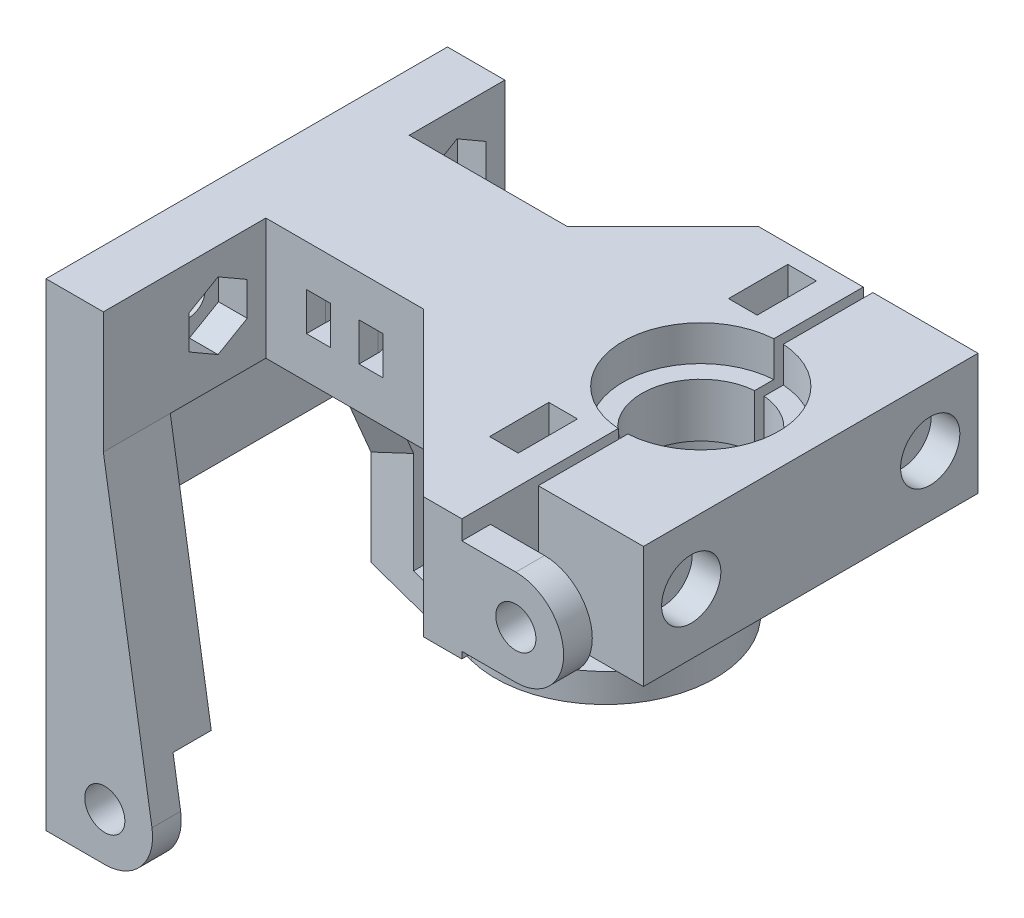
SolidWorks part; units mm, degrees
note: The reader was unsure of these and kept them because the rebuilt part matched: shared geometry of "草圖14<3>", "草圖43<3>", "草圖34<5>", "草圖48<3>".
ref_plane "前基準面" through (0, 0, 0) normal (0, 0, 1) x (1, 0, 0)
ref_plane "上基準面" through (0, 0, 0) normal (0, 1, 0) x (1, 0, 0)
ref_plane "右基準面" through (0, 0, 0) normal (1, 0, 0) x (0, 0, -1)
sketch "草圖13" plane through (0, 0, 0) normal (0, 1, 0) x (1, 0, 0)
  line L0 (0, 0) -> (44, 0) construction
  line L1 (0, 0) -> (0, 17.5)
  line L2 (0, 0) -> (0, -17.5)
  line L3 (0, 17.5) -> (6, 17.5)
  line L4 (6, 17.5) -> (6, -17.5)
  line L5 (6, -17.5) -> (0, -17.5)
  line L6 (6, 7.5) -> (32.5, 7.5)
  line L7 (6, -7.5) -> (32.5, -7.5)
  line L8 (32.5, 17.5) -> (22.5, 7.5)
  line L9 (32.5, -17.5) -> (55.5, -17.5)
  line L10 (32.5, -17.5) -> (32.5, 17.5)
  line L11 (32.5, 17.5) -> (55.5, 17.5)
  line L12 (55.5, -17.5) -> (55.5, 17.5)
  line L13 (32.5, -17.5) -> (55.5, 17.5) construction
  line L14 (32.5, 17.5) -> (55.5, -17.5) construction
  line L15 (32.5, -17.5) -> (22.5, -7.5)
  line L16 (32.5, 7.5) -> (22.5, 7.5)
  line L17 (22.5, -7.5) -> (32.5, -7.5)
  circle A0 centre (44, 0) radius 8.15
  circle A1 centre (44, 0) radius 6.15
  point P17 (44, 0)
  dimension "D4" = 35
  dimension "D5" = 12.3
  dimension "D6" = 23
  dimension "D1" = 16.3
  dimension "D2" = 35
  dimension "D3" = 6
  dimension "D7" = 15
  dimension "D8" = 10
  dimension "D9" = 44
extrude "填料-伸長4" add sketch "草圖13" against normal blind 12.7
sketch "草圖17" plane through (0, 0, 0) normal (0, 1, 0) x (1, 0, 0)
  circle A0 centre (44, 0) radius 6.15
  circle A1 centre (44, 0) radius 8.15
  circle A2 centre (44, 0) radius 6.15 construction
  circle A3 centre (44, 0) radius 8.15 construction
  circle M29 centre (44, 0) radius 6.15
ref_plane "平面4" through (44, 0, 0) normal (-1, 0, 0) x (0, 0, 1)
sketch "草圖14" plane through (55.5, 0, 0) normal (-1, 0, 0) x (0, 0, 1)
  line L0 (17.5, -6.35) -> (7.5, -6.35) construction
  line L3 (-7.5, -6.35) -> (-17.5, -6.35) construction
  line L5 (-17.5, -12.7) -> (-17.5, 0) construction
  line L6 (17.5, -12.7) -> (17.5, 0) construction
  line L9 (7.5, -12.7) -> (7.5, 0) construction
  line L10 (-7.5, -12.7) -> (-7.5, 0) construction
  circle A0 centre (-12.5, -6.35) radius 1.65
  circle A1 centre (12.5, -6.35) radius 1.65
  circle A2 centre (12.5, -6.35) radius 3.1
  circle A3 centre (-12.5, -6.35) radius 3.1
  dimension "D1" = 3.3
  dimension "D2" = 6.2
sketch "草圖15" plane through (44, 0, 0) normal (-1, 0, 0) x (0, 0, 1)
  line L1 (17.5, 0) -> (-17.5, 0)
  line L2 (17.5, 0) -> (17.5, -12.7)
  line L3 (17.5, -12.7) -> (-17.5, -12.7)
  line L4 (-17.5, 0) -> (-17.5, -12.7)
extrude "除料-伸長11" cut sketch "草圖15" against normal blind 0.5 and the other way blind 0.5
extrude "除料-伸長12" cut sketch "草圖14" along normal blind 3 contours A3 A0 | A2 A1
extrude "除料-伸長13" cut sketch "草圖14<3>" along normal blind 25 contours A0 | A1
sketch "草圖14<3>" plane through (55.5, 0, 0) normal (-1, 0, 0) x (0, 0, 1) same geometry as "草圖14"
ref_plane "平面5" through (37.5, 0, 0) normal (1, 0, 0) x (0, 0, -1)
sketch "草圖16" plane through (37.5, 0, 0) normal (1, 0, 0) x (0, 0, -1)
  line L0 (-17.5, 0) -> (17.5, 0) construction
  line L1 (-15.6, -12.7) -> (-9.4, -12.7)
  line L2 (-15.6, -12.7) -> (-15.6, 0)
  line L3 (-15.6, 0) -> (-9.4, 0)
  line L4 (-9.4, -12.7) -> (-9.4, 0)
  line L5 (-15.6, -12.7) -> (-9.4, 0) construction
  line L6 (-15.6, 0) -> (-9.4, -12.7) construction
  line L8 (9.4, -12.7) -> (15.6, -12.7)
  line L9 (9.4, -12.7) -> (9.4, 0)
  line L10 (9.4, 0) -> (15.6, 0)
  line L11 (15.6, -12.7) -> (15.6, 0)
  line L12 (9.4, -12.7) -> (15.6, 0) construction
  line L13 (9.4, 0) -> (15.6, -12.7) construction
  point P0 (-12.5, -6.35)
  point P8 (12.5, -6.35)
  dimension "D1" = 6.2
extrude "除料-伸長14" cut sketch "草圖16" along normal blind 3
extrude "除料-伸長30" cut sketch "草圖17" against normal blind 3.7 contours A1 M29
sketch "草圖18" plane through (0, -12.7, 0) normal (0, -1, 0) x (1, 0, 0)
  circle A0 centre (44, 0) radius 8.15
  circle A1 centre (44, 0) radius 8.15 construction
  circle A2 centre (44, 0) radius 6.15
  circle A3 centre (44, 0) radius 6.15 construction
  line M5 (43.5, 6.1296) -> (43.5, 17.5)
  line M17 (43.5, -17.5) -> (43.5, -6.1296)
  arc M18 (43.5, -6.1296) -> (43.5, 6.1296) centre (44, 0) cw
extrude "除料-伸長31" cut sketch "草圖18" against normal blind 3.4 contours A2 A0 M17 M5 | A0 M5 M17 M18
sketch "草圖19" plane through (0, 0, 0) normal (-1, 0, 0) x (0, 0, 1)
  line L0 (0, 0) -> (0, -12.7) construction
  line L1 (17.5, -12.7) -> (-17.5, -12.7) construction
  line L2 (-12.5, -6.35) -> (12.5, -6.35) construction
  circle A0 centre (-12.5, -6.35) radius 1.65
  circle A1 centre (12.5, -6.35) radius 1.65
  point P8 (0, -6.35)
  dimension "D2" = 3.3
  dimension "D1" = 25
extrude "除料-伸長32" cut sketch "草圖19" against normal up to surface (6 mm away) up to face at (6, -6.35, 12.5)
sketch "草圖20" plane through (6, 0, 0) normal (1, 0, 0) x (0, 0, -1)
  line L1 (-12.5, -2.8282) -> (-15.55, -4.5891)
  line L2 (-15.55, -4.5891) -> (-15.55, -8.1109)
  line L3 (-15.55, -8.1109) -> (-12.5, -9.8718)
  line L4 (-12.5, -9.8718) -> (-9.45, -8.1109)
  line L5 (-9.45, -8.1109) -> (-9.45, -4.5891)
  line L6 (-9.45, -4.5891) -> (-12.5, -2.8282)
  line L7 (12.5, -2.8282) -> (9.45, -4.5891)
  line L8 (9.45, -4.5891) -> (9.45, -8.1109)
  line L9 (9.45, -8.1109) -> (12.5, -9.8718)
  line L10 (12.5, -9.8718) -> (15.55, -8.1109)
  line L11 (15.55, -8.1109) -> (15.55, -4.5891)
  line L12 (15.55, -4.5891) -> (12.5, -2.8282)
  circle A0 centre (-12.5, -6.35) radius 3.05 construction
  circle A1 centre (12.5, -6.35) radius 3.05 construction
  dimension "D1" = 6.1
extrude "除料-伸長33" cut sketch "草圖20" against normal blind 3
sketch "草圖21" plane through (0, -12.7, 0) normal (0, -1, 0) x (1, 0, 0)
  line L0 (0, -17.5) -> (6, -17.5) construction
  line L1 (0, 17.5) -> (3, 17.5)
  line L2 (0, 17.5) -> (0, -17.5)
  line L3 (0, -17.5) -> (3, -17.5)
  line L4 (3, 17.5) -> (3, -17.5)
  dimension "D1" = 3
extrude "填料-伸長5" add sketch "草圖21" along normal blind 10
ref_plane "平面6" through (0, 0, 24.5) normal (0, 0, 1) x (1, 0, 0)
sketch "草圖22" plane through (0, 0, 24.5) normal (0, 0, 1) x (1, 0, 0)
  line L0 (0, 0) -> (0, -50)
  line L1 (0, -50) -> (6.15, -50)
  line L2 (6.15, -45) -> (49.15, -45) construction
  line L3 (49.15, -45) -> (49.15, -7) construction
  line L4 (0, 0) -> (6, 0)
  line L5 (6, -12.7) -> (11.0861, -44.2031)
  line L6 (6, 0) -> (6, -12.7)
  line L8 (49.15, -2) -> (43.5, -2)
  line L10 (43.5, -12.7) -> (43.5, 0) construction
  line L11 (43.5, -2) -> (43.5, 0)
  line L13 (43.5, 0) -> (38, 0)
  line L14 (32.5, 0) -> (43.5, 0) construction
  line L15 (38, 0) -> (38, -12.7)
  line L16 (32.5, -12.7) -> (43.5, -12.7) construction
  line L17 (38, -12.7) -> (43.5, -12.7)
  line L18 (43.5, -12.7) -> (43.5, -12)
  line L19 (43.5, -12) -> (49.15, -12)
  circle A0 centre (49.15, -7) radius 2.1
  circle A1 centre (6.15, -45) radius 2.1
  circle A2 centre (6.15, -45) radius 5
  circle A3 centre (49.15, -7) radius 5
  dimension "D5" = 4.2
  dimension "D4" = 10
  dimension "D1" = 38
  dimension "D2" = 43
  dimension "D3" = 45
  dimension "D6" = 6.15
ref_plane "平面9" through (0, -6.35, 0) normal (0, 1, 0) x (1, 0, 0)
extrude "填料-伸長6" add sketch "草圖22" against normal up to surface (7 mm away)
sketch "草圖41" plane through (0, 0, 17.5) normal (0, 0, -1) x (-1, 0, 0)
  line L1 (-13.6797, -50.7245) -> (1.3797, -50.7245)
  line L2 (-13.6797, -50.7245) -> (-13.6797, -39.2755)
  line L3 (-13.6797, -39.2755) -> (1.3797, -39.2755)
  line L4 (1.3797, -50.7245) -> (1.3797, -39.2755)
  line L5 (-13.6797, -50.7245) -> (1.3797, -39.2755) construction
  line L6 (-13.6797, -39.2755) -> (1.3797, -50.7245) construction
  point P0 (-6.15, -45)
extrude "除料-伸長34" cut sketch "草圖41" against normal blind 4
sketch "草圖42" plane through (0, -2, 0) normal (0, 1, 0) x (1, 0, 0)
  line L0 (54.15, -24.5) -> (54.15, -17.5) construction
  line L1 (43.5, -17.5) -> (54.15, -17.5)
  line L2 (43.5, -17.5) -> (43.5, -21.5)
  line L3 (43.5, -21.5) -> (54.15, -21.5)
  line L4 (54.15, -17.5) -> (54.15, -21.5)
  dimension "D1" = 4
extrude "除料-伸長35" cut sketch "草圖42" against normal up to surface (10 mm away) up to face at (45.96, -12, 20.3)
sketch "草圖43" plane through (0, 0, 0) normal (0, 1, 0) x (1, 0, 0)
  line L0 (32.5, -17.5) -> (39.5, -24.5)
  line L1 (43.5, -24.5) -> (38, -24.5) construction
  line L2 (39.5, -24.5) -> (32.5, -24.5)
  line L3 (32.5, -17.5) -> (32.5, -24.5)
  line L4 (32.5, -17.5) -> (38, -17.5)
  line L5 (38, -17.5) -> (38, -23)
  line L6 (38, -17.5) -> (38, -24.5) construction
  line L7 (32.5, -17.5) -> (22.5, -7.5) construction
  line M16 (32.5, -17.5) -> (38, -17.5)
  line M17 (38, -17.5) -> (38, -24.5)
  line M18 (38, -24.5) -> (43.5, -24.5)
extrude "除料-伸長36" cut sketch "草圖43" against normal up to surface (12.7 mm away) contours L0 M17 M18 up to face at (23.8969, -12.7, 1.9688)
extrude "填料-伸長7" add sketch "草圖43<3>" against normal up to surface (12.7 mm away) contours L0 M16 M17 up to face at (39, -12.7, -12.5)
sketch "草圖43<3>" plane through (0, 0, 0) normal (0, 1, 0) x (1, 0, 0) same geometry as "草圖43"
sketch "草圖34" plane through (6, 0, 0) normal (1, 0, 0) x (0, 0, -1)
  line L0 (17.5, -12.7) -> (9.5, -12.7)
  line L1 (9.5, -22.7) -> (9.5, -42.7)
  line L2 (9.5, -42.7) -> (24.5, -42.7)
  line L3 (17.5, -16.2009) -> (24.5, -32.7)
  line L4 (17.5, -12.7) -> (8.1346, -12.7) construction
  line L5 (9.5, -12.7) -> (9.5, -22.7)
  line L6 (9.5, -32.7) -> (5.2574, -22.7)
  line L7 (17.5, -12.7) -> (24.5, -12.7)
  line L8 (24.5, -12.7) -> (24.5, -42.7)
  line L9 (17.5, -22.7) -> (-17.5, -22.7) construction
  line L10 (5.2574, -22.7) -> (9.5, -22.7)
  line L11 (17.5, -22.7) -> (17.5, -12.7) construction
  line L12 (-17.5, -12.7) -> (17.5, -12.7) construction
  line L13 (5.2574, -22.7) -> (5.2574, -12.7)
  line L14 (-8.1346, -12.7) -> (8.1346, -12.7) construction
  line L15 (5.2574, -12.7) -> (9.5, -12.7)
  line L16 (9.5, -12.7) -> (9.4752, -12.712)
  line L17 (17.5, -12.7) -> (17.5, -16.2009)
  line L18 (9.5, -22.7) -> (17.5, -22.7)
  line L19 (17.5, -22.7) -> (17.5, -16.2009)
  dimension "D1" = 20
  dimension "D2" = 3.5009
  dimension "D3" = 8
  dimension "D4" = 10
  dimension "D5" = 20
  dimension "D6" = 7
extrude "填料-伸長8" add sketch "草圖34" against normal up to surface (6 mm away) contours L19 L18 L1 L2 L8 L3 | L10 L6 L1 up to face at (0, -6.35, 14.15)
sketch "草圖44" plane through (0, -42.7, 0) normal (0, -1, 0) x (1, 0, 0)
  line L0 (0, -24.5) -> (14.134, -28.1372)
  line L1 (0, -9.5) -> (14.134, -5.8628)
  line L2 (0, -9.5) -> (0, -24.5)
  line L5 (0, -9.5) -> (6, -9.5) construction
  line L6 (0, -24.5) -> (0, -9.5) construction
  circle A0 centre (17, -17) radius 11.5
  circle A1 centre (17, -17) radius 6.5
  line M1 (0, -9.5) -> (0, -24.5)
  line M2 (0, -24.5) -> (6, -24.5)
  line M3 (6, -24.5) -> (6, -9.5)
  line M4 (6, -9.5) -> (0, -9.5)
  dimension "D2" = 13
  dimension "D3" = 23
  dimension "D1" = 17
  dimension "D4" = 17
extrude "填料-伸長9" add sketch "草圖44" against normal blind 3 contours A0 A1 M3 | A0 M3 | A0 M3 M4 M1 M2 | A0 L0 M3 M2 | A0 L1 M4 M3
extrude "填料-伸長14" add sketch "草圖34<5>" against normal up to surface (3 mm away) up to face at (3, -19.9501, -6.7096)
sketch "草圖34<5>" plane through (6, 0, 0) normal (1, 0, 0) x (0, 0, -1) same geometry as "草圖34"
sketch "草圖39" plane through (0, -6.35, 0) normal (0, 1, 0) x (1, 0, 0)
  line L0 (6, -7.5) -> (14.25, -7.5) construction
  line L1 (6, -7.5) -> (22.5, -7.5) construction
  line L2 (14.25, -7.5) -> (14.25, -5.5) construction
  line L3 (12.75, -5.5) -> (12.75, -7.5)
  line L4 (15.75, -5.5) -> (15.75, -7.5)
  line L5 (10.25, -5.5) -> (10.25, -7.5)
  line L6 (13.25, -5.5) -> (13.25, -7.5)
  line L7 (18.25, -5.5) -> (18.25, -7.5)
  line L8 (15.75, -7.5) -> (18.25, -7.5)
  line L9 (10.25, -7.5) -> (12.75, -7.5)
  circle A0 centre (14.25, -5.5) radius 1.5
  circle A1 centre (14.25, -5.5) radius 4
  dimension "D2" = 3
  dimension "D1" = 2
  dimension "D3" = 2.5
extrude "除料-伸長37" cut sketch "草圖39" against normal blind 2 and the other way blind 2 contours L8 A1 L9 L3 A0 L4 | A1 L5 L9 | A1 L8 L7
sketch "草圖46" plane through (52.5, 0, 0) normal (1, 0, 0) x (0, 0, -1)
  circle A0 centre (-12.5, -6.35) radius 1.65
  circle A1 centre (12.5, -6.35) radius 1.65
extrude "填料-伸長12" add sketch "草圖46" against normal blind 0.2
sketch "草圖47" plane through (40.5, 0, 0) normal (-1, 0, 0) x (0, 0, 1)
  circle A0 centre (12.5, -6.35) radius 1.65
  circle A1 centre (-12.5, -6.35) radius 1.65
extrude "填料-伸長13" add sketch "草圖47" against normal blind 0.2
sketch "草圖48" plane through (0, -39.7, 0) normal (0, 1, 0) x (1, 0, 0)
  line L0 (6, 24.5) -> (6, 26.044)
  line L1 (0, 24.5) -> (14.134, 28.1372) construction
  line L2 (6, 26.044) -> (0, 24.5)
  line L3 (0, 24.5) -> (6, 24.5)
  line L4 (0, 9.5) -> (6, 7.956)
  line L5 (6, 17.5) -> (6, 7.5) construction
  line L6 (0, 9.5) -> (14.134, 5.8628) construction
  line L7 (6, 7.956) -> (6, 9.5)
  line L8 (0, 9.5) -> (6, 9.5)
  line M1 (6, 9.5) -> (0, 9.5)
  line M2 (0, 9.5) -> (14.134, 5.8628)
  line M4 (14.134, 28.1372) -> (0, 24.5)
  line M5 (0, 24.5) -> (6, 24.5)
extrude "填料-伸長15" add sketch "草圖48" along normal up to surface (3.3608 mm away) contours L0 M5 M4
extrude "填料-伸長16" add sketch "草圖48<3>" along normal up to surface (7 mm away) contours L7 M2 M1
sketch "草圖48<3>" plane through (0, -39.7, 0) normal (0, 1, 0) x (1, 0, 0) same geometry as "草圖48"
